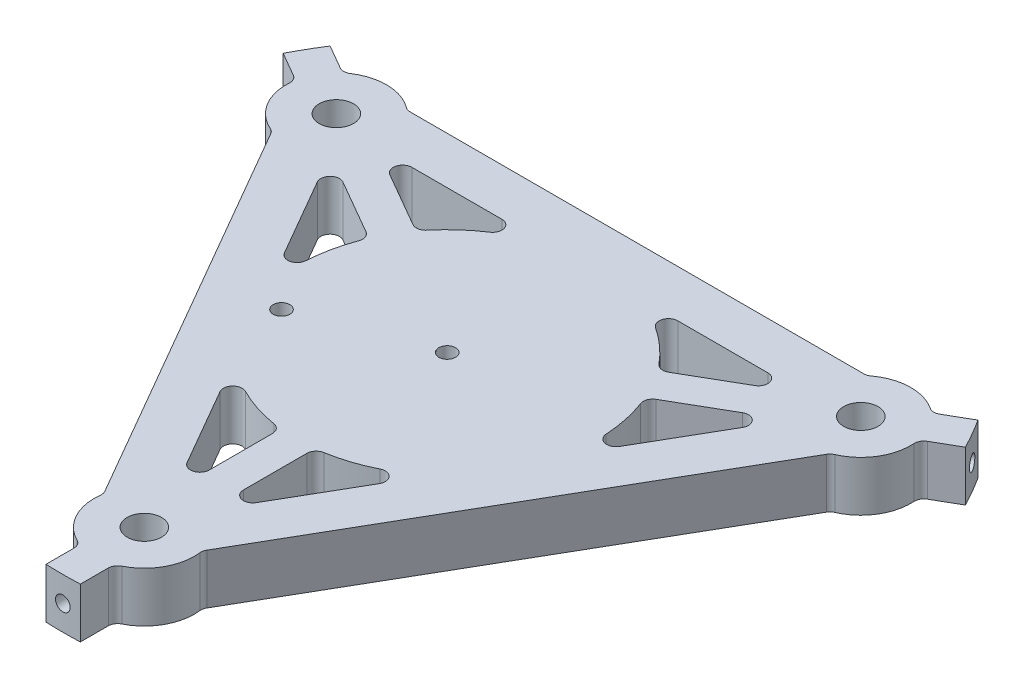
SolidWorks part; units mm, degrees
material "6061-T4 (SS)"
ref_plane "Front Plane" through (0, 0, 0) normal (0, 0, 1) x (1, 0, 0)
ref_plane "Top Plane" through (0, 0, 0) normal (0, 1, 0) x (1, 0, 0)
ref_plane "Right Plane" through (0, 0, 0) normal (1, 0, 0) x (0, 0, -1)
sketch "Sketch1" plane through (0, 0, 0) normal (0, 1, 0) x (1, 0, 0)
  line L0 (-3.2639, -67.6472) -> (-3.2639, -72.952)
  line L1 (3.2639, -67.6472) -> (3.2639, -72.952)
  line L2 (3.2639, -41.9471) -> (3.2639, -29.9313)
  line L3 (-3.2639, -41.9471) -> (-3.2639, -29.9313)
  line L4 (-34.6953, 23.8002) -> (-24.2893, 17.7923)
  line L5 (-37.9592, 18.1469) -> (-27.5532, 12.139)
  line L6 (-56.9522, 36.6502) -> (-61.5464, 39.3026)
  line L7 (-60.2161, 30.997) -> (-64.8103, 33.6494)
  line L8 (37.9592, 18.1469) -> (27.5532, 12.139)
  line L9 (34.6953, 23.8002) -> (24.2893, 17.7923)
  line L10 (60.2161, 30.997) -> (64.8103, 33.6494)
  line L11 (56.9522, 36.6502) -> (61.5464, 39.3026)
  line L12 (0, 0) -> (0, -57.531) construction
  line L13 (0, 0) -> (-49.8233, 28.7655) construction
  line L14 (0, 0) -> (49.8233, 28.7655) construction
  line L15 (40.388, 15.7181) -> (31.8393, 0.9115)
  line L16 (9.6892, -55.3504) -> (52.7795, 19.2841)
  line L17 (-6.5817, -42.8361) -> (-15.1303, -28.0294)
  line L18 (-52.7795, 19.2841) -> (-9.6892, -55.3504)
  line L19 (-43.0903, 36.0663) -> (43.0903, 36.0663)
  line L20 (-33.8063, 27.118) -> (-16.709, 27.118)
  line L21 (16.709, 27.118) -> (33.8063, 27.118)
  line L22 (-31.8393, 0.9115) -> (-40.388, 15.7181)
  line L23 (15.1303, -28.0294) -> (6.5817, -42.8361)
  arc A0 (-3.2639, -72.952) -> (3.2639, -72.952) centre (0, 0) ccw
  arc A1 (4.7466, -28.178) -> (12.7944, -25.5506) centre (0, 0) ccw
  arc A2 (-9.4626, -56.4426) -> (-4.2488, -66.0559) centre (0, -57.531) ccw
  circle A3 centre (0, -57.531) radius 3.2639
  arc A4 (4.2488, -66.0559) -> (9.4626, -56.4426) centre (0, -57.531) ccw
  arc A5 (-44.1494, 36.4162) -> (-55.0817, 36.7075) centre (-49.8233, 28.7655) ccw
  arc A6 (-61.5464, 39.3026) -> (-64.8103, 33.6494) centre (0, 0) ccw
  arc A7 (-59.3305, 29.3484) -> (-53.612, 20.0264) centre (-49.8233, 28.7655) ccw
  circle A8 centre (-49.8233, 28.7655) radius 3.2639
  arc A9 (53.612, 20.0264) -> (59.3305, 29.3484) centre (49.8233, 28.7655) ccw
  arc A10 (64.8103, 33.6494) -> (61.5464, 39.3026) centre (0, 0) ccw
  arc A11 (55.0817, 36.7075) -> (44.1494, 36.4162) centre (49.8233, 28.7655) ccw
  circle A12 centre (49.8233, 28.7655) radius 3.2639
  arc A13 (-26.7762, 9.9784) -> (-28.5247, 1.695) centre (0, 0) ccw
  arc A14 (22.0296, 18.1997) -> (15.7302, 23.8556) centre (0, 0) ccw
  circle A15 centre (0, 0) radius 1.5875
  arc A16 (-12.7944, -25.5506) -> (-4.7466, -28.178) centre (0, 0) ccw
  arc A17 (28.5247, 1.695) -> (26.7762, 9.9784) centre (0, 0) ccw
  arc A18 (-15.7302, 23.8556) -> (-22.0296, 18.1997) centre (0, 0) ccw
  arc A19 (37.9592, 18.1469) -> (40.388, 15.7181) centre (38.8482, 16.6071) cw
  arc A20 (26.7762, 9.9784) -> (27.5532, 12.139) centre (28.4422, 10.5992) cw
  arc A21 (3.2639, -29.9313) -> (4.7466, -28.178) centre (5.0419, -29.9313) cw
  arc A22 (15.1303, -28.0294) -> (12.7944, -25.5506) centre (13.5905, -27.1404) ccw
  arc A23 (6.5817, -42.8361) -> (3.2639, -41.9471) centre (5.0419, -41.9471) cw
  arc A24 (-6.5817, -42.8361) -> (-3.2639, -41.9471) centre (-5.0419, -41.9471) ccw
  arc A25 (-3.2639, -29.9313) -> (-4.7466, -28.178) centre (-5.0419, -29.9313) ccw
  arc A26 (-15.1303, -28.0294) -> (-12.7944, -25.5506) centre (-13.5905, -27.1404) cw
  arc A27 (-31.8393, 0.9115) -> (-28.5247, 1.695) centre (-30.2996, 1.8005) ccw
  arc A28 (-26.7762, 9.9784) -> (-27.5532, 12.139) centre (-28.4422, 10.5992) ccw
  arc A29 (-40.388, 15.7181) -> (-37.9592, 18.1469) centre (-38.8482, 16.6071) cw
  arc A30 (-24.2893, 17.7923) -> (-22.0296, 18.1997) centre (-23.4003, 19.3321) ccw
  arc A31 (-34.6953, 23.8002) -> (-33.8063, 27.118) centre (-33.8063, 25.34) cw
  arc A32 (-15.7302, 23.8556) -> (-16.709, 27.118) centre (-16.709, 25.34) ccw
  arc A33 (-4.2488, -66.0559) -> (-3.2639, -67.6472) centre (-5.0419, -67.6472) cw
  arc A34 (3.2639, -67.6472) -> (4.2488, -66.0559) centre (5.0419, -67.6472) cw
  arc A35 (9.6892, -55.3504) -> (9.4626, -56.4426) centre (11.229, -56.2394) ccw
  arc A36 (-9.4626, -56.4426) -> (-9.6892, -55.3504) centre (-11.229, -56.2394) ccw
  arc A37 (-52.7795, 19.2841) -> (-53.612, 20.0264) centre (-54.3193, 18.3951) ccw
  arc A38 (-59.3305, 29.3484) -> (-60.2161, 30.997) centre (-61.1051, 29.4572) ccw
  arc A39 (-56.9522, 36.6502) -> (-55.0817, 36.7075) centre (-56.0632, 38.19) ccw
  arc A40 (-44.1494, 36.4162) -> (-43.0903, 36.0663) centre (-43.0903, 37.8443) ccw
  arc A41 (43.0903, 36.0663) -> (44.1494, 36.4162) centre (43.0903, 37.8443) ccw
  arc A42 (52.7795, 19.2841) -> (53.612, 20.0264) centre (54.3193, 18.3951) cw
  arc A43 (55.0817, 36.7075) -> (56.9522, 36.6502) centre (56.0632, 38.19) ccw
  arc A44 (59.3305, 29.3484) -> (60.2161, 30.997) centre (61.1051, 29.4572) cw
  arc A45 (15.7302, 23.8556) -> (16.709, 27.118) centre (16.709, 25.34) cw
  arc A46 (34.6953, 23.8002) -> (33.8063, 27.118) centre (33.8063, 25.34) ccw
  arc A47 (22.0296, 18.1997) -> (24.2893, 17.7923) centre (23.4003, 19.3321) ccw
  arc A48 (31.8393, 0.9115) -> (28.5247, 1.695) centre (30.2996, 1.8005) cw
  point P53 (18.9808, -21.3603)
  point P64 (-27.9889, -5.7577)
  point P77 (-3.2639, -66.4793)
  point P80 (3.2639, -66.4793)
  point P103 (9.0082, 27.118)
  dimension "D1" = 146.05
  dimension "D2" = 57.15
  dimension "D3" = 19.05
  dimension "D4" = 6.5278
  dimension "D9" = 3.175
  dimension "D10" = 1.778
  dimension "D11" = 1.778
  dimension "D5" = 57.531
  dimension "D7" = 120
  dimension "D8" = 120
  dimension "D6" = 3
extrude "Boss-Extrude1" add sketch "Sketch1" along normal mid plane 9.525
sketch "Sketch2" plane through (0, 0, 0) normal (0, 0, 1) x (1, 0, 0)
  line L0 (0, 4.7625) -> (0, -4.7625) construction
  line L1 (3.2639, 4.7625) -> (-3.2639, 4.7625) construction
  line L2 (-3.2639, -4.7625) -> (3.2639, -4.7625) construction
ref_plane "Plane1" through (0, 0, 73.025) normal (0, 0, 1) x (1, 0, 0)
sketch "Sketch3" plane through (0, 0, 73.025) normal (0, 0, 1) x (1, 0, 0)
  circle A0 centre (0, 0) radius 1.397
  dimension "D1" = 2.794
extrude "Cut-Extrude1" cut sketch "Sketch3" against normal blind 6.35
pattern_circular "CirPattern1" count 3 over 360 about axis through (0, 4.7625, 0) along (0, -1, 0) of "Cut-Extrude1"
sketch "Sketch4" plane through (0, -4.7625, 0) normal (0, -1, 0) x (1, 0, 0)
  circle A0 centre (-22.821, 8.6514) radius 1.5875
  dimension "D1" = 3.175
extrude "Cut-Extrude2" cut sketch "Sketch4" against normal through all both and the other way through all
